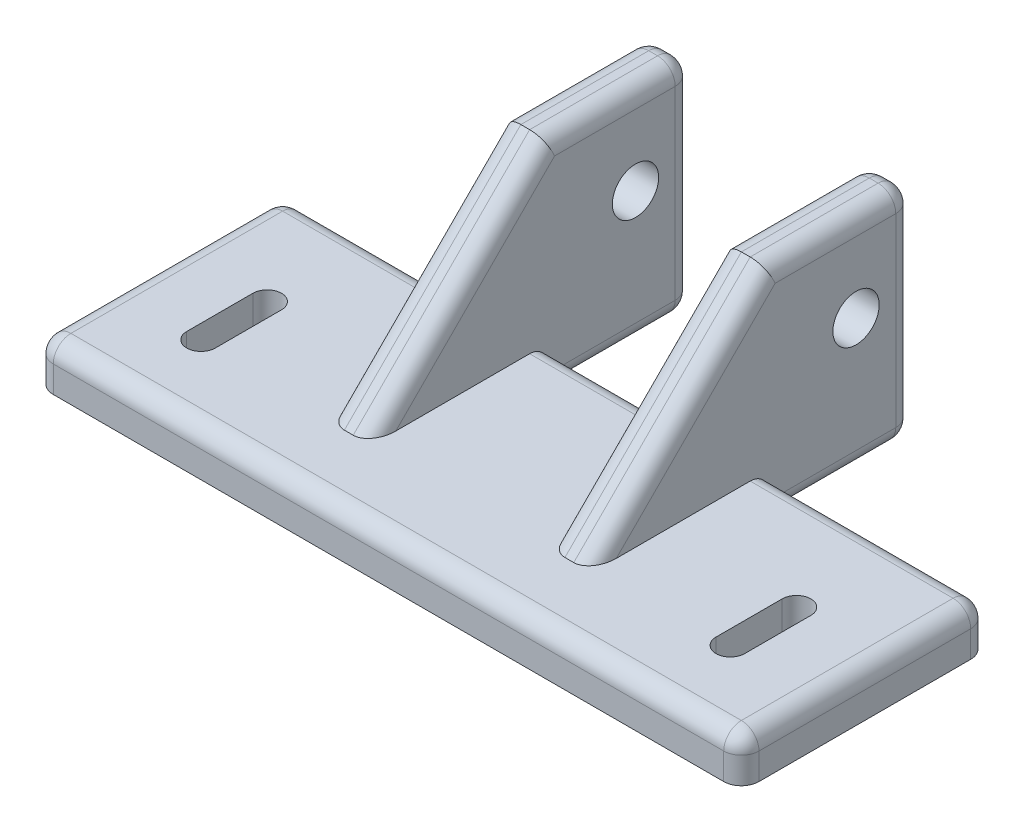
SolidWorks part; units mm, degrees
note: The reader was unsure of these and kept them because the rebuilt part matched: shared geometry of "Sketch1<3>", "Sketch1<4>", "Sketch1<6>", "Sketch1<7>", "Sketch1<8>".
ref_plane "Front Plane" through (0, 0, 0) normal (0, 0, 1) x (1, 0, 0)
ref_plane "Top Plane" through (0, 0, 0) normal (0, 1, 0) x (1, 0, 0)
ref_plane "Right Plane" through (0, 0, 0) normal (1, 0, 0) x (0, 0, -1)
sketch "Sketch1" plane through (0, 0, 0) normal (1, 0, 0) x (0, 0, -1)
  line L0 (-10, -10) -> (6.5, -10)
  line L5 (-10, 10) -> (6.5, 10)
  line L7 (-10, -15) -> (6.5, -15)
  line L8 (6.5, 10) -> (6.5, -15)
  line L9 (-10, -10) -> (-38, -10)
  line L10 (-38, -10) -> (-38, -15)
  line L11 (-38, -15) -> (-10, -15)
  line L12 (6.5, 10) -> (10, 10) construction
  line L13 (10, 10) -> (10, -15) construction
  line L14 (10, -15) -> (6.5, -15) construction
  line L15 (-10, -10) -> (-10, 10)
  line L16 (-10, -15) -> (-10, -10)
  line L17 (-13, -10) -> (-13, -15) construction
  line L18 (-25.5, -10) -> (-25.5, -15) construction
  line L19 (-10, 10) -> (-30, -10)
  circle A0 centre (0, 0) radius 2.625
  point P4 (-10, 0)
  point P6 (0, 0)
  dimension "D9" = 5.25
  dimension "D1" = 20
  dimension "D2" = 10
  dimension "D3" = 20
  dimension "D4" = 5
  dimension "D5" = 3.5
  dimension "D6" = 3
  dimension "D7" = 25
  dimension "D8" = 12.5
  dimension "D10" = 45
extrude "Boss-Extrude1" add sketch "Sketch1" along normal blind 5 from offset 10 contours L15 L0 L8 L5
extrude "Boss-Extrude2" add sketch "Sketch1<3>" against normal blind 5 from offset 10 separate body contours L15 L0 L8 L5 offset against normal yes
sketch "Sketch1<3>" plane through (0, 0, 0) normal (1, 0, 0) x (0, 0, -1) same geometry as "Sketch1"
extrude "Boss-Extrude3" add sketch "Sketch1<4>" along normal up to surface and the other way up to surface contours L16 L7 L8 L0 | L11 L16 L9 L10
sketch "Sketch1<4>" plane through (0, 0, 0) normal (1, 0, 0) x (0, 0, -1) same geometry as "Sketch1"
sketch "Sketch2" plane through (0, -10, 0) normal (0, 1, 0) x (1, 0, 0)
  line L0 (-15, -10) -> (-40, -10)
  line L1 (-40, -10) -> (-40, -38)
  line L2 (-40, -38) -> (-15, -38)
  line L3 (-15, -10) -> (-15, -38)
  line L4 (0, -1000) -> (0, 49000) construction
  line L5 (15, -10) -> (15, -38)
  line L6 (40, -38) -> (15, -38)
  line L7 (40, -10) -> (40, -38)
  line L8 (15, -10) -> (40, -10)
  line L9 (-30, -29.25) -> (-30, -21.75) construction
  line L10 (-31.625, -29.25) -> (-31.625, -21.75)
  line L11 (-28.375, -29.25) -> (-28.375, -21.75)
  line L12 (30, -29.25) -> (30, -21.75) construction
  line L13 (31.625, -29.25) -> (31.625, -21.75)
  line L14 (28.375, -29.25) -> (28.375, -21.75)
  arc A0 (-31.625, -29.25) -> (-28.375, -29.25) centre (-30, -29.25) ccw
  arc A1 (-28.375, -21.75) -> (-31.625, -21.75) centre (-30, -21.75) ccw
  arc A2 (31.625, -29.25) -> (28.375, -29.25) centre (30, -29.25) cw
  arc A3 (28.375, -21.75) -> (31.625, -21.75) centre (30, -21.75) cw
  point P6 (-30, -25.5)
  point P13 (30, -25.5)
  point P14 (-30, -25.5)
  point P24 (30, -25.5)
  line M6 (-15, -10) -> (-15, -38)
  line M8 (15, -38) -> (15, -10)
  dimension "D4" = 1.625
  dimension "D1" = 12.5
  dimension "D2" = 60
  dimension "D3" = 10
  dimension "D5" = 7.5
extrude "Boss-Extrude4" add sketch "Sketch2" against normal up to surface (5 mm away) contours L1 L2 L0 M6 | L8 L6 L7 M8
extrude "Cut-Extrude1" cut sketch "Sketch1<6>" along normal up to surface and the other way up to surface contours L16 L7 L8 L0 up to face at (10, 0, -2.625) other way up to face at (-10, 0, -2.625)
sketch "Sketch1<6>" plane through (0, 0, 0) normal (1, 0, 0) x (0, 0, -1) same geometry as "Sketch1"
extrude "Boss-Extrude5" add sketch "Sketch1<7>" along normal up to surface (5 mm away) from surface at 10 contours L15 L19 L9 up to face at (15, -4, 3.4) starting at face at (10, 0, -2.625)
sketch "Sketch1<7>" plane through (0, 0, 0) normal (1, 0, 0) x (0, 0, -1) same geometry as "Sketch1"
extrude "Boss-Extrude6" add sketch "Sketch1<8>" against normal up to surface (5 mm away) from surface at -10 contours L15 L19 L9 up to face at (-15, -4, 3.4) starting at face at (-10, 0, -2.625)
sketch "Sketch1<8>" plane through (0, 0, 0) normal (1, 0, 0) x (0, 0, -1) same geometry as "Sketch1"
fillet "Fillet1" radius 2 30 edges at (12.5, 10, -6.5) (-10, 0, 20) (-15, 0, 20) (12.5, -15, -6.5) (-15, -2.5, -6.5) (0, -10, 38) (-15, -15, 1.75) (15, -2.5, -6.5) (15, 10, 1.75) (-10, 10, 1.75) (-10, -2.5, -6.5) (-12.5, 10, -6.5) (-15, 10, 1.75) (15, -15, 1.75) (-40, -12.5, 38) (-40, -12.5, 10) (-40, -10, 24) (-27.5, -10, 10) (27.5, -10, 10) (40, -12.5, 10) (40, -10, 24) (40, -12.5, 38) (10, 10, 1.75) (10, -2.5, -6.5) (-12.5, -15, -6.5) (10, -15, 1.75) (0, -10, 10) (-10, -15, 1.75) (10, 0, 20) (15, 0, 20)
equation "\"D8@Sketch1\"=\"D7@Sketch1\"/2"
